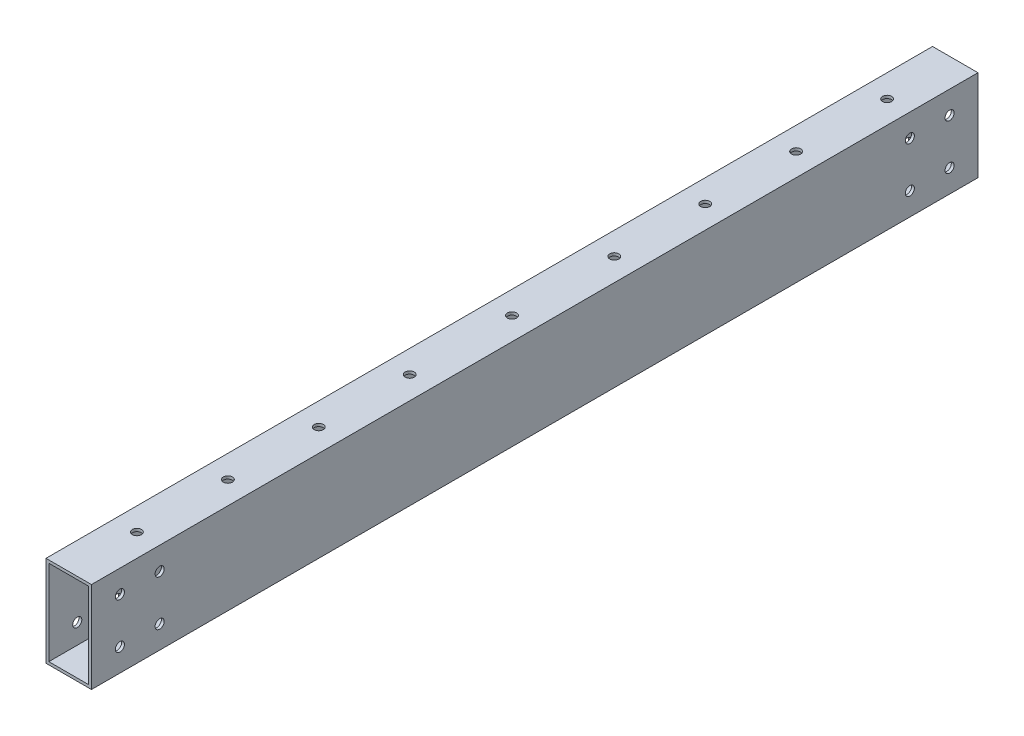
SolidWorks part; units mm, degrees
ref_plane "Front Plane" through (0, 0, 0) normal (0, 0, 1) x (1, 0, 0)
ref_plane "Top Plane" through (0, 0, 0) normal (0, 1, 0) x (1, 0, 0)
ref_plane "Right Plane" through (0, 0, 0) normal (1, 0, 0) x (0, 0, -1)
sketch "Sketch1" plane through (0, 0, 0) normal (0, 0, 1) x (1, 0, 0)
  line L0 (11.1125, -23.8125) -> (-11.1125, 23.8125) construction
  line L1 (-12.7, -25.4) -> (12.7, -25.4)
  line L2 (-12.7, -25.4) -> (-12.7, 25.4)
  line L3 (-12.7, 25.4) -> (12.7, 25.4)
  line L4 (12.7, -25.4) -> (12.7, 25.4)
  line L5 (-11.1125, -23.8125) -> (11.1125, -23.8125)
  line L6 (-11.1125, -23.8125) -> (-11.1125, 23.8125)
  line L7 (-11.1125, 23.8125) -> (11.1125, 23.8125)
  line L8 (11.1125, -23.8125) -> (11.1125, 23.8125)
  dimension "D1" = 25.4
  dimension "D2" = 50.8
  dimension "D3" = 1.5875
  dimension "D4" = 1.5875
  dimension "D5" = 1.5875
  dimension ".0625" = 1.5875
extrude "Boss-Extrude1" add sketch "Sketch1" along normal blind 495.3
sketch "Sketch2" plane through (12.7, 0, 0) normal (1, 0, 0) x (0, 0, -1)
  line L0 (-247.65, 25.4) -> (-247.65, -25.4) construction
  line L1 (-495.3, 0) -> (-479.425, 0) construction
  line L2 (-495.3, -25.4) -> (0, -25.4) construction
  line L3 (-479.425, 12.7) -> (-479.425, -12.7) construction
  line L4 (-495.3, 25.4) -> (0, 25.4) construction
  line L5 (-495.3, -25.4) -> (-495.3, 25.4) construction
  circle A5 centre (-479.425, -12.7) radius 2.54
  circle A6 centre (-457.2, -12.7) radius 2.54
  circle A7 centre (-479.425, 12.7) radius 2.54
  circle A8 centre (-457.2, 12.7) radius 2.54
  circle A9 centre (-38.1, 12.7) radius 2.54
  circle A10 centre (-15.875, 12.7) radius 2.54
  circle A11 centre (-38.1, -12.7) radius 2.54
  circle A12 centre (-15.875, -12.7) radius 2.54
  dimension "D2" = 5.08
  dimension "D9" = 15.875
  dimension "D10" = 38.1
  dimension "D11" = 12.7
extrude "Cut-Extrude1" cut sketch "Sketch2" against normal through all
sketch "Sketch3" plane through (0, 25.4, 0) normal (0, 1, 0) x (1, 0, 0)
  line L0 (12.7, -247.65) -> (-12.7, -247.65) construction
  line L1 (12.7, -495.3) -> (12.7, 0) construction
  line L2 (-12.7, -495.3) -> (-12.7, 0) construction
  line L3 (12.7, -495.3) -> (-12.7, -495.3) construction
  circle A0 centre (0, -457.2) radius 2.54
  circle A1 centre (0, -406.4) radius 2.54
  circle A2 centre (0, -355.6) radius 2.54
  circle A3 centre (0, -304.8) radius 2.54
  circle A6 centre (0, -190.5) radius 2.54
  circle A7 centre (0, -139.7) radius 2.54
  circle A8 centre (0, -88.9) radius 2.54
  circle A9 centre (0, -38.1) radius 2.54
  circle A10 centre (0, -247.65) radius 2.54
  dimension "D3" = 5.08
  dimension "D1" = 12.7
  dimension "D2" = 38.1
  dimension "D4" = 4
extrude "Cut-Extrude2" cut sketch "Sketch3" against normal through all
